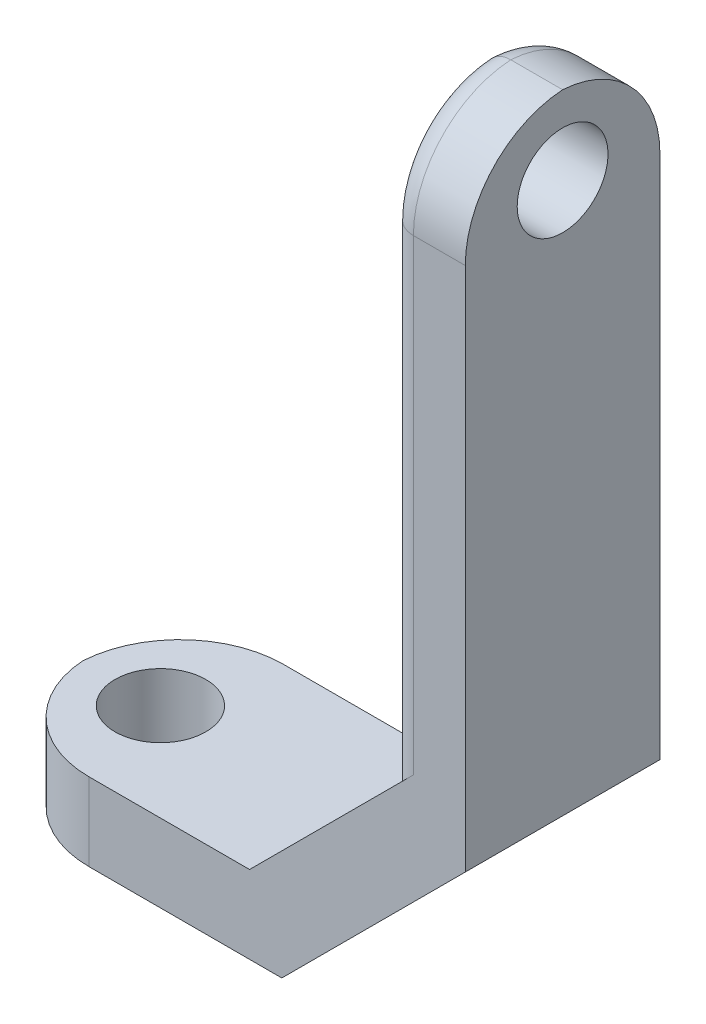
SolidWorks part; units mm, degrees
material "ABS"
ref_plane "前视基准面" through (0, 0, 0) normal (0, 0, 1) x (1, 0, 0)
ref_plane "上视基准面" through (0, 0, 0) normal (0, 1, 0) x (1, 0, 0)
ref_plane "右视基准面" through (0, 0, 0) normal (1, 0, 0) x (0, 0, -1)
sketch "草图1" plane through (0, 0, 0) normal (0, 0, 1) x (1, 0, 0)
  line L0 (0, 0) -> (0, -6)
  line L1 (0, -6) -> (22.8579, -6)
  line L2 (22.8579, -6) -> (37, 8.1421)
  line L3 (37, 8.1421) -> (37, 56.6274)
  line L4 (37, 56.6274) -> (31, 56.6274)
  line L5 (31, 56.6274) -> (31, 10.6274)
  line L6 (31, 10.6274) -> (20.3726, 0)
  line L7 (20.3726, 0) -> (0, 0)
  dimension "D1" = 6
  dimension "D2" = 20.3726
  dimension "D3" = 6
  dimension "D4" = 45
  dimension "D5" = 46
  dimension "D6" = 6
  dimension "D7" = 20
extrude "凸台-拉伸1" add sketch "草图1" along normal blind 15
sketch "草图3" plane through (0, 0, 0) normal (0, 1, 0) x (1, 0, 0)
  line L0 (0, -7.5) -> (20.3726, -7.5) construction
  line L1 (0, -15) -> (0, 0) construction
  line L2 (20.3726, -15) -> (20.3726, 0) construction
  circle A0 centre (6, -7.5) radius 3.5
  dimension "D1" = 7
  dimension "D2" = 6
extrude "切除-拉伸1" cut sketch "草图3" against normal through all
sketch "草图4" plane through (31, 0, 0) normal (-1, 0, 0) x (0, 0, 1)
  line L0 (7.5, 10.6274) -> (7.5, 56.6274) construction
  line L1 (15, 10.6274) -> (0, 10.6274) construction
  line L2 (15, 56.6274) -> (0, 56.6274) construction
  circle A0 centre (7.5, 50.5685) radius 3.5
  dimension "D1" = 7
  dimension "D2" = 39.9411
extrude "切除-拉伸2" cut sketch "草图4" against normal through all
fillet "圆角1" radius 8 4 edges at (0, -3, 15) (0, -3, 0) (34, 56.6274, 0) (34, 56.6274, 15)
fillet "圆角4" radius 2 4 edges at (31, 54.1046, 12.831) (31, 54.1046, 2.169) (31, 29.6274, 15) (31, 29.6274, 0)
